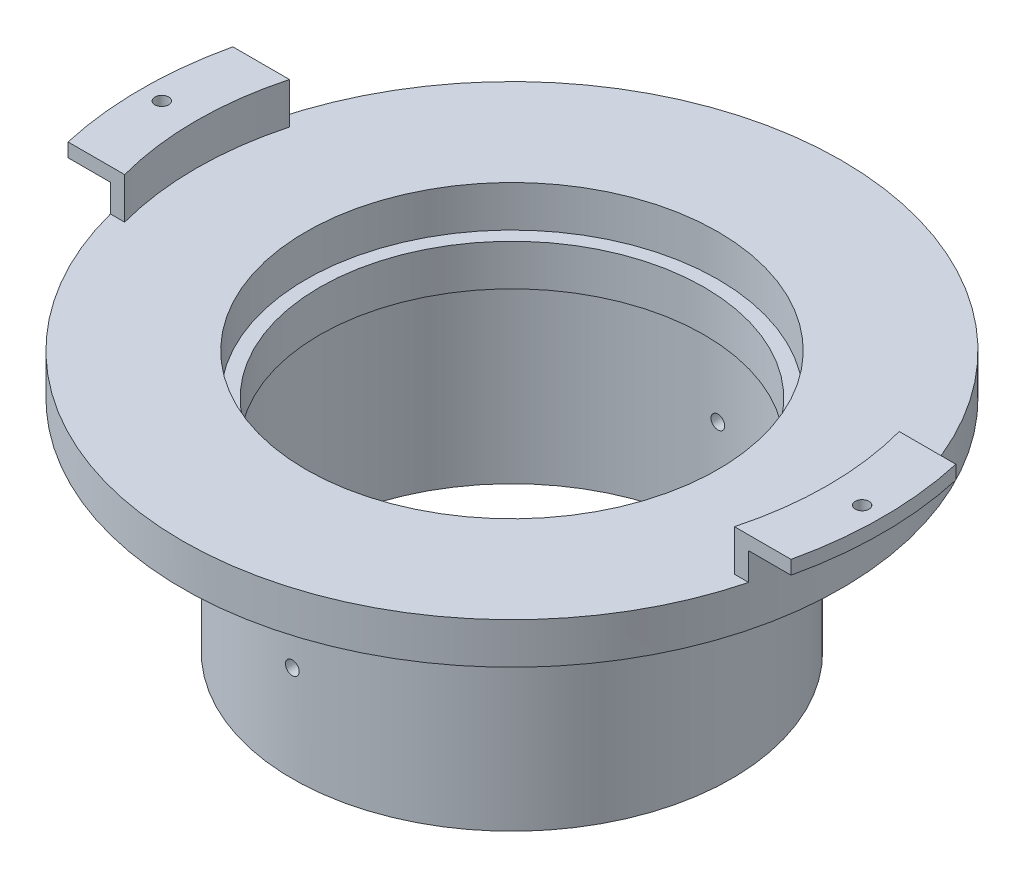
SolidWorks part; units mm, degrees
ref_plane "Front Plane" through (0, 0, 0) normal (0, 0, 1) x (1, 0, 0)
ref_plane "Top Plane" through (0, 0, 0) normal (0, 1, 0) x (1, 0, 0)
ref_plane "Right Plane" through (0, 0, 0) normal (1, 0, 0) x (0, 0, -1)
sketch "Sketch1" plane through (0, 0, 0) normal (0, 0, 1) x (1, 0, 0)
  line L0 (-80, -95) -> (-80, -15)
  line L25 (-80, -15) -> (-120, -15)
  line L26 (-120, -15) -> (-120, 10)
  line L27 (-120, 10) -> (-135, 10)
  line L28 (-135, 10) -> (-135, 15)
  line L29 (-135, 15) -> (-115, 15)
  line L30 (-115, 15) -> (-115, 0)
  line L31 (-115, 0) -> (-75, 0)
  line L32 (-70, -15) -> (-70, -30)
  line L35 (-70, -30) -> (-75, -30)
  line L36 (-75, -30) -> (-75, -95)
  line L37 (-75, -95) -> (-80, -95)
  line L41 (-70, -15) -> (-75, -15)
  line L42 (-75, 0) -> (-75, -15)
  dimension "D2" = 5
  dimension "D3" = 5
  dimension "D5" = 30
  dimension "D6" = 15
  dimension "D7" = 15
  dimension "D8" = 5
  dimension "D9" = 75
  dimension "D10" = 80
  dimension "D11" = 20
  dimension "D12" = 5
  dimension "D13" = 40
ref_axis "Axis1" through (0, -100.5, 0) along (0, 1, 0)
revolve "Revolve1" add sketch "Sketch1" angle 360 about axis through (0, -100.5, 0) along (0, 1, 0)
sketch "Sketch2" plane through (0, 10, 0) normal (0, -1, 0) x (1, 0, 0)
  circle A0 centre (127.5, 0) radius 2.5
  circle A1 centre (-127.5, 0) radius 2.5
  circle A2 centre (0, 0) radius 120 construction
  dimension "D1" = 5
  dimension "D3" = 127.5
  dimension "D2" = 127.5
extrude "Cut-Extrude3" cut sketch "Sketch2" against normal up to surface (5 mm away) up to face at (0, 15, -135)
sketch "Sketch3" plane through (0, 15, 0) normal (0, 1, 0) x (1, 0, 0)
  line L0 (-111.018, -30) -> (-131.6245, -30)
  line L1 (131.6245, -30) -> (111.018, -30)
  line L5 (131.6245, 30) -> (111.018, 30)
  line L9 (-111.018, 30) -> (-131.6245, 30)
  circle A0 centre (0, 0) radius 135 construction
  circle A1 centre (-127.5, 0) radius 2.5 construction
  arc A2 (-131.6245, -30) -> (131.6245, -30) centre (0, 0) ccw
  circle A3 centre (0, 0) radius 115 construction
  arc A4 (-111.018, -30) -> (111.018, -30) centre (0, 0) ccw
  arc A5 (111.018, 30) -> (-111.018, 30) centre (0, 0) ccw
  arc A6 (131.6245, 30) -> (-131.6245, 30) centre (0, 0) ccw
  dimension "D2" = 30
  dimension "D1" = 30
extrude "Cut-Extrude4" cut sketch "Sketch3" against normal up to surface (15 mm away) up to face at (0, 0, -115)
sketch "Sketch6" plane through (0, 0, 0) normal (0, 0, 1) x (1, 0, 0)
  line L0 (0, -100.5) -> (0, 20.5) construction
  line L1 (-80, -95) -> (80, -95) construction
  circle A0 centre (0, -60) radius 2.5
  dimension "D1" = 5
  dimension "D2" = 35
extrude "Cut-Extrude6" cut sketch "Sketch6" against normal through all both and the other way through all
